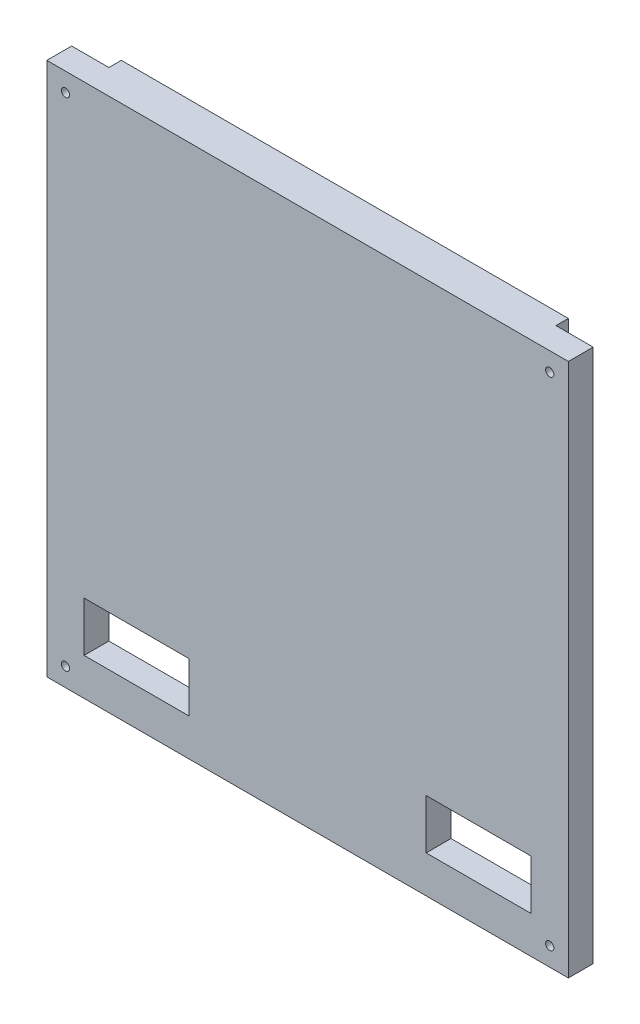
SolidWorks part; units mm, degrees
ref_plane "Front Plane" through (0, 0, 0) normal (0, 0, 1) x (1, 0, 0)
ref_plane "Top Plane" through (0, 0, 0) normal (0, 1, 0) x (1, 0, 0)
ref_plane "Right Plane" through (0, 0, 0) normal (1, 0, 0) x (0, 0, -1)
sketch "Sketch3" plane through (0, 0, 0) normal (0, 1, 0) x (1, 0, 0)
  line L0 (-105, 0) -> (105, 0)
  line L1 (105, 0) -> (105, -10)
  line L2 (105, -10) -> (-105, -10)
  line L3 (-105, -10) -> (-105, 0)
  dimension "D1" = 210
  dimension "D2" = 10
extrude "Boss-Extrude1" add sketch "Sketch3" along normal blind 215
ref_plane "Plane1" through (0, 45, 0) normal (0, 1, 0) x (1, 0, 0)
sketch "Sketch5" plane through (0, 215, 0) normal (0, 1, 0) x (1, 0, 0)
  line L0 (-90, 0) -> (-90, 5)
  line L1 (105, 0) -> (-105, 0) construction
  line L2 (-90, 5) -> (90, 5)
  line L3 (90, 5) -> (90, 0)
  line L4 (-105, 0) -> (-105, -10) construction
  line L5 (105, 0) -> (90, 0)
  line L9 (-105, 0) -> (-105, -10)
  line L10 (-105, -10) -> (105, -10)
  line L11 (105, -10) -> (105, 0)
  line L12 (105, 0) -> (-105, 0)
  line L13 (-105, 0) -> (-105, -10)
  line L14 (-105, -10) -> (105, -10)
  line L15 (105, -10) -> (105, 0)
  line L16 (-90, 0) -> (-105, 0)
  dimension "D1" = 180
  dimension "D2" = 5
  dimension "D3" = 15
  dimension "D4" = 0
extrude "Boss-Extrude2" add sketch "Sketch5" against normal up to surface (170 mm away) up to plane "Plane1"
sketch "Sketch6" plane through (0, 45, 0) normal (0, 1, 0) x (1, 0, 0)
  line L0 (-80, 0) -> (-80, 15)
  line L2 (-80, 15) -> (80, 15)
  line L3 (80, 15) -> (80, 0)
  line L4 (80, 0) -> (-80, 0)
  line L6 (90, 5) -> (-90, 5) construction
  dimension "D1" = 160
  dimension "D2" = 10
extrude "Boss-Extrude3" add sketch "Sketch6" against normal blind 10
sketch "Sketch7" plane through (0, 0, 10) normal (0, 0, 1) x (1, 0, 0)
  line L0 (0, -1000) -> (0, 49000) construction
  line L1 (-105, 215) -> (105, 215) construction
  line L2 (-105, 215) -> (-105, 0) construction
  line L3 (55, 0) -> (-55, 0) construction
  circle A0 centre (-97.5, 207.5) radius 1.65
  circle A1 centre (-97.5, 7.5) radius 1.65
  circle A2 centre (97.5, 7.5) radius 1.65
  circle A3 centre (97.5, 207.5) radius 1.65
  dimension "D1" = 3.3
  dimension "D2" = 7.5
  dimension "D4" = 7.5
  dimension "D3" = 7.5
  dimension "D5" = 7.5
extrude "Cut-Extrude1" cut sketch "Sketch7" against normal up to surface (10 mm away) up to face at (0, 92.5, 0)
sketch "Sketch8" plane through (0, 0, 10) normal (0, 0, 1) x (1, 0, 0)
  line L0 (-105, 215) -> (-105, 0) construction
  line L1 (-90, 35) -> (-47.75, 35)
  line L2 (-90, 35) -> (-90, 15)
  line L3 (-90, 15) -> (-47.75, 15)
  line L4 (-47.75, 35) -> (-47.75, 15)
  line L5 (-105, 0) -> (105, 0) construction
  line L6 (0, -1000) -> (0, 49000) construction
  line L7 (90, 15) -> (47.75, 15)
  line L8 (47.75, 35) -> (47.75, 15)
  line L9 (90, 35) -> (47.75, 35)
  line L10 (90, 35) -> (90, 15)
  dimension "D1" = 15
  dimension "D2" = 15
  dimension "D3" = 42.25
  dimension "D4" = 20
extrude "Cut-Extrude2" cut sketch "Sketch8" against normal up to surface (10 mm away) up to face at (99.15, 207.5, 0)
